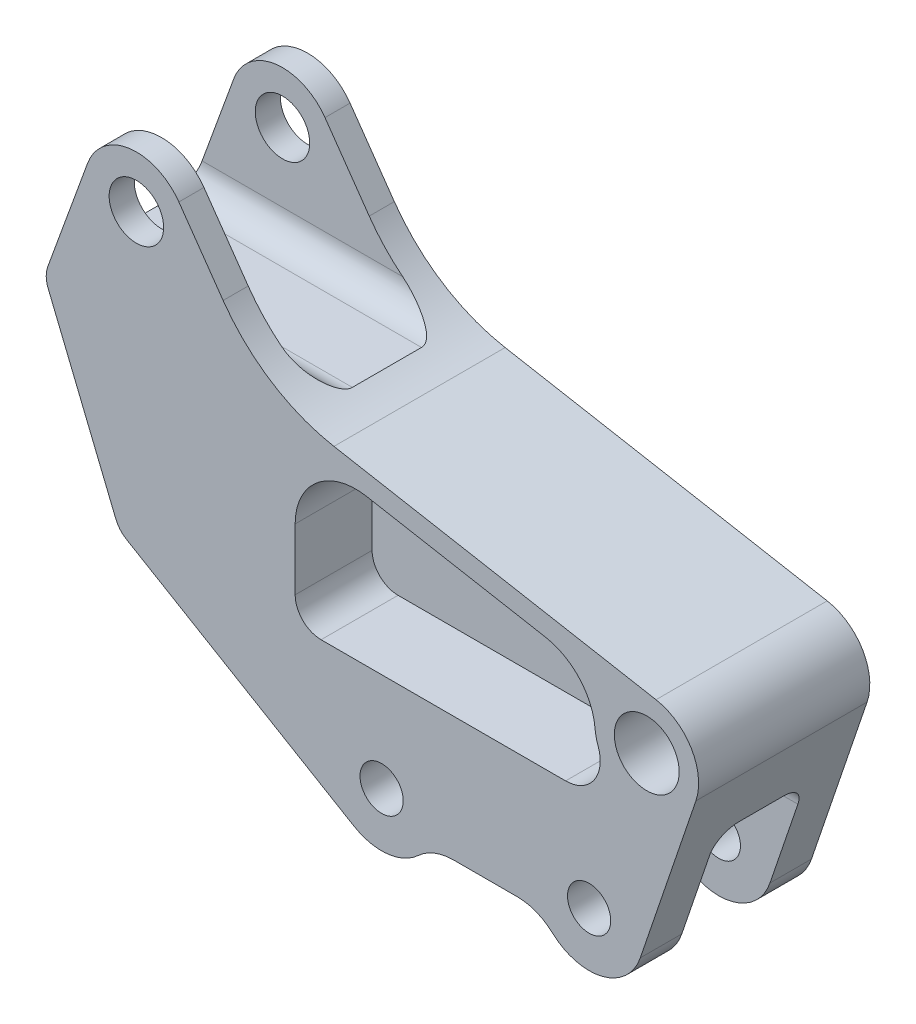
SolidWorks part; units mm, degrees
material "6061-T6 (SS)"
ref_plane "Front Plane" through (0, 0, 0) normal (1, 0, 0) x (0, 1, 0)
ref_plane "Top Plane" through (0, 0, 0) normal (0, 0, 1) x (0, 1, 0)
ref_plane "Right Plane" through (0, 0, 0) normal (0, 1, 0) x (-1, 0, 0)
sketch "Sketch1" plane through (0, 0, 0) normal (0, 0, 1) x (0, 1, 0)
  line L0 (-26.4994, 0.9506) -> (-2.45, -7.2154)
  line L1 (-27.7573, 15.43) -> (-27.7573, 31.9833)
  line L6 (16.5445, 88.4856) -> (34.0097, 82.1288)
  line L7 (-11.2473, 51.6467) -> (-11.2473, -4.2282)
  line L8 (35.7742, 68.7264) -> (26.4934, 62.228)
  line L9 (7.4979, -1.3585) -> (16.0691, 45.9497)
  line L11 (-9.4693, 53.4247) -> (15.6555, 53.4247)
  line L12 (-9.4693, 47.8367) -> (-9.4693, 11.9174)
  line L13 (-5.6593, 51.6467) -> (3.3583, 51.6467)
  line L15 (17.4335, 88.1621) -> (17.4335, 50.7405)
  line L16 (15.6555, 88.1229) -> (15.6555, 53.4247)
  line L17 (7.3396, 14.865) -> (12.1058, 41.1718)
  line L20 (16.5445, 57.1222) -> (6.8134, 3.412) construction
  line L21 (16.5445, 88.4856) -> (16.5445, 57.1222) construction
  line L22 (16.5445, 57.1222) -> (41.0622, 41.4215) construction
  line L32 (-25.6569, 51.6467) -> (-11.2473, 51.6467)
  line L33 (-30.779, 42.988) -> (-10.3583, 77.5084)
  line L34 (-10.3583, 77.5084) -> (16.5445, 88.4856)
  line L38 (-10.3583, -4.5301) -> (-10.3583, 77.5084) construction
  line L39 (-9.4693, 53.4247) -> (-9.4693, 77.8711)
  line L40 (-10.3583, 52.5357) -> (-25.131, 52.5357) construction
  line L41 (-24.6052, 53.4247) -> (-11.2473, 53.4247)
  line L42 (-11.2473, 53.4247) -> (-11.2473, 76.0056)
  line L43 (31.4035, 74.9684) -> (17.4335, 74.9684) construction
  circle A0 centre (0, 0) radius 4.7625
  circle A1 centre (31.4035, 74.9684) radius 4
  circle A2 centre (-23.9473, 38.9467) radius 3.175
  circle A3 centre (-23.9473, 8.4667) radius 3.175
  arc A4 (-2.45, -7.2154) -> (7.4979, -1.3585) centre (0, 0) ccw
  arc A5 (-30.779, 42.988) -> (-27.7573, 31.9833) centre (-23.9473, 38.9467) ccw
  arc A6 (35.7742, 68.7264) -> (34.0097, 82.1288) centre (31.4035, 74.9684) ccw
  arc A7 (-27.7573, 15.43) -> (-26.4994, 0.9506) centre (-23.9473, 8.4667) ccw
  arc A8 (26.4934, 62.228) -> (16.0691, 45.9497) centre (41.0622, 41.4215) ccw
  arc A10 (-9.4693, 47.8367) -> (-5.6593, 51.6467) centre (-5.6593, 47.8367) cw
  arc A13 (3.3583, 51.6467) -> (12.1058, 41.1718) centre (3.3583, 42.7567) cw
  arc A14 (-9.4693, 11.9174) -> (-2.6336, 7.1504) centre (-4.3893, 11.9174) ccw
  arc A15 (-2.6336, 7.1504) -> (-0.6498, 7.5922) centre (0, 0) cw
  arc A16 (-0.6498, 7.5922) -> (7.3396, 14.865) centre (-1.4079, 16.4499) ccw
  point P55 (19.6722, 55.1192)
  dimension "D1" = 9.525
  dimension "D2" = 6.35
  dimension "D3" = 8
  dimension "D4" = 6.35
  dimension "D10" = 1.778
  dimension "D11" = 15.24
  dimension "D12" = 15.875
  dimension "D13" = 15.875
  dimension "D14" = 15.24
  dimension "D18" = 25.4
  dimension "D22" = 3.048
  dimension "D23" = 3.81
  dimension "D29" = 8.89
  dimension "D30" = 5.08
  dimension "D31" = 8.89
  dimension "D39" = 2.54
  dimension "D34" = 12.7
  dimension "D19" = 35
  dimension "D35" = 1.778
  dimension "D5" = 81.28
  dimension "D6" = 45.72
  dimension "D7" = 66.04
  dimension "D8" = 25.4
  dimension "D9" = 30.48
  dimension "D15" = 12.7
  dimension "D16" = 13.97
  dimension "D17" = 12.7
  dimension "D20" = 1.778
  dimension "D21" = 3.81
  dimension "D24" = 20
  dimension "D25" = 3.81
extrude "Boss-Extrude1" add sketch "Sketch1" along normal blind 12.573 contours A8 L15 L8 L7 L0 A4 L9 L16 L11 A16 A15 A14 L12 A10 L13 A13 L17 A0 | A8 L8 L15 | L8 A6 A1 | L1 A7 L0 L7 A5 A2 A3 | L41 L42 L34 L33 | L39 L11 L16 L34 region at (-25.0117, -19.949, 0) region at (-23.7092, -10.1941, 0) region at (-60.9516, -15.7, 0) region at (-72.6999, 25.1629, 0) region at (-68.3589, 3.8189, 0)
extrude "Boss-Extrude2" add sketch "Sketch1<4>" along normal blind 1.27 contours A15 A16 L17 A13 L13 A10 L12 A14 region at (-30.7751, 0.07, 0)
sketch "Sketch1<4>" plane through (0, 0, 0) normal (0, 0, 1) x (0, 1, 0) same geometry as "Sketch1"
extrude "Cut-Extrude1" cut sketch "Sketch1<6>" along normal blind 6.477 contours L1 A7 L0 L7 L32 L33 A5 A2 A3 region at (-25.0117, -19.949, 0)
sketch "Sketch1<6>" plane through (0, 0, 0) normal (0, 0, 1) x (0, 1, 0) same geometry as "Sketch1"
extrude "Cut-Extrude3" cut sketch "Sketch1<10>" along normal blind 8.89 contours A8 L8 A6 L6 L15 A1 | L41 L42 L33 | L39 L11 L16 L34 region at (-60.9516, -15.7, 0) region at (-72.6999, 25.1629, 0) region at (-68.3589, 3.8189, 0)
sketch "Sketch1<10>" plane through (0, 0, 0) normal (0, 0, 1) x (0, 1, 0) same geometry as "Sketch1"
mirror "Mirror1" about plane through (0, 0, 0) normal (0, 0, 1) of bodies 107 103
sketch "Sketch3" plane through (0, 0, 0) normal (0, 0, 1) x (0, 1, 0)
  line L0 (-23.9473, 38.9467) -> (31.4035, 74.9684) construction
  line L1 (-11.2473, 51.6467) -> (-11.2473, -4.2282) construction
  line L2 (-23.9473, 38.9467) -> (-118.6003, -15.7012) construction
  line L3 (31.4035, 74.9684) -> (85.9954, 47.2192) construction
  circle A0 centre (31.4035, 74.9684) radius 4 construction
  circle A1 centre (-23.9473, 38.9467) radius 3.175 construction
  dimension "D1" = 120
  dimension "D2" = 60
fillet "Fillet1" radius 3.81 10 edges at (-69.4513, 17.4335, 8.89) (-51.6467, -18.4521, 6.477) (-51.6467, -18.4521, -6.477) (-53.4247, -17.9263, 8.89) (-53.4247, -17.9263, -8.89) (-70.7738, 15.6555, 8.89) (-65.6479, -9.4693, 8.89) (-65.6479, -9.4693, -8.89) (-70.7738, 15.6555, -8.89) (-69.4513, 17.4335, -8.89)
fillet "Fillet3" radius 3.81 2 edges at (-77.5084, -10.3583, 0) (-88.4856, 16.5445, 0)
fillet "Fillet4" radius 3.175 10 edges at (-21.8042, -11.2473, 6.477) (-21.8042, -11.2473, -6.477) (-50.5307, -11.2473, 5.3611) (-51.6467, -11.2473, 0) (-50.5307, -11.2473, -5.3611) (-53.4247, -11.2473, 0) (-66.6201, -11.2473, 8.89) (-54.5406, -11.2473, 7.7741) (-66.6201, -11.2473, -8.89) (-54.5406, -11.2473, -7.7741)
fillet "Fillet5" radius 7.62 4 edges at (-15.43, -27.7573, 9.525) (-31.9833, -27.7573, 9.525) (-15.43, -27.7573, -9.525) (-31.9833, -27.7573, -9.525)
